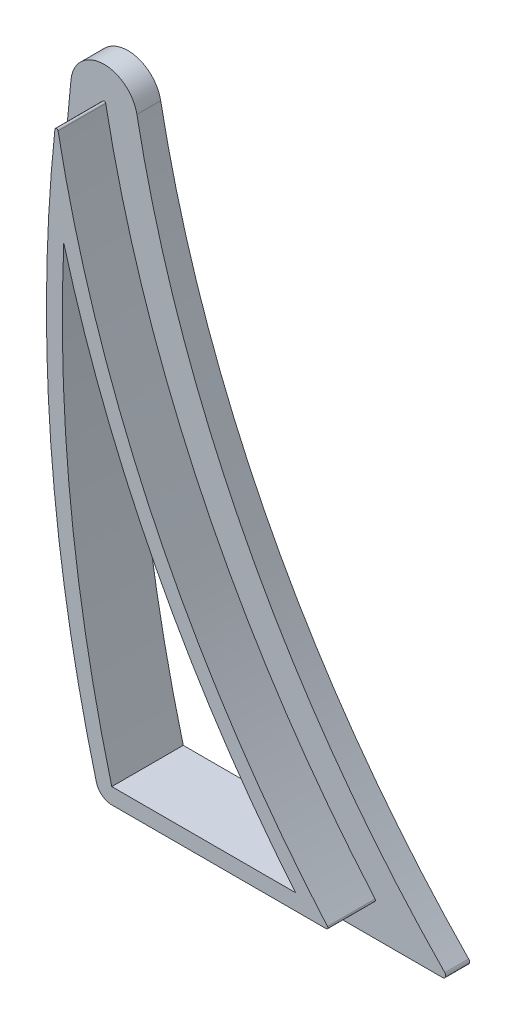
SolidWorks part; units mm, degrees
ref_plane "Plan de face" through (0, 0, 0) normal (0, 0, 1) x (1, 0, 0)
ref_plane "Plan de dessus" through (0, 0, 0) normal (0, 1, 0) x (1, 0, 0)
ref_plane "Plan de droite" through (0, 0, 0) normal (1, 0, 0) x (0, 0, -1)
sketch "Esquisse1" plane through (0, 0, 0) normal (0, 0, 1) x (1, 0, 0)
  line L2 (-4.5246, -18.1471) -> (9.1989, -18.1471)
  line L3 (-4.5246, -17.1471) -> (7.0417, -17.1471)
  arc A6 (-8.0323, 17.5812) -> (9.1989, -18.1471) centre (65.7323, 31.1376) ccw
  arc A7 (-5.4914, -17.4024) -> (-4.5246, -18.1471) centre (-4.5246, -17.1471) ccw
  arc A8 (-8.0323, 17.5812) -> (-5.4914, -17.4024) centre (86.36, 6.8529) ccw
  arc A9 (-7.5489, 10.9915) -> (7.0417, -17.1471) centre (65.7323, 31.1376) ccw
  arc A10 (-7.5489, 10.9915) -> (-4.5246, -17.1471) centre (86.36, 6.8529) ccw
extrude "Boss.-Extru.1" add sketch "Esquisse1" along normal blind 3 contours A6 A8 A7 L2 A10 A9 L3 region at (-4.8911, -17.623, 0)
fillet "Congé1" radius 0.1 1 edges at (-8.0323, 17.5812, 1.5)
sketch "Esquisse2" plane through (0, 0, 3) normal (0, 0, 1) x (1, 0, 0)
  line L0 (-4.5246, -20.1471) -> (13.7815, -20.1471)
  line L1 (-4.5246, -18.1471) -> (9.1989, -18.1471)
  line L2 (-4.5246, -18.1471) -> (9.1989, -18.1471)
  line L3 (-4.5246, -17.1471) -> (7.0417, -17.1471) construction
  line L4 (-4.5246, -17.1471) -> (7.0417, -17.1471)
  arc A0 (-10.0945, 17.1256) -> (-7.4252, -17.9131) centre (86.36, 6.8529) ccw
  arc A1 (-7.4252, -17.9131) -> (-4.5246, -20.1471) centre (-4.5246, -17.1471) ccw
  arc A2 (-5.9444, 17.3012) -> (13.7815, -20.1471) centre (65.7323, 31.1376) ccw
  arc A3 (-5.9444, 17.3012) -> (-10.0945, 17.1256) centre (-8.0064, 16.9032) ccw
  arc A4 (-7.9082, 16.9222) -> (9.1989, -18.1471) centre (65.7323, 31.1376) ccw
  arc A5 (-7.9082, 16.9222) -> (-8.1058, 16.9138) centre (-8.0064, 16.9032) ccw
  arc A6 (-8.1058, 16.9138) -> (-5.4914, -17.4024) centre (86.36, 6.8529) ccw
  arc A7 (-5.4914, -17.4024) -> (-4.5246, -18.1471) centre (-4.5246, -17.1471) ccw
  arc A8 (-7.9082, 16.9222) -> (9.1989, -18.1471) centre (65.7323, 31.1376) ccw
  arc A9 (-7.9082, 16.9222) -> (-8.1058, 16.9138) centre (-8.0064, 16.9032) ccw
  arc A10 (-8.1058, 16.9138) -> (-5.4914, -17.4024) centre (86.36, 6.8529) ccw
  arc A11 (-5.4914, -17.4024) -> (-4.5246, -18.1471) centre (-4.5246, -17.1471) ccw
  arc A12 (-7.5489, 10.9915) -> (-4.5246, -17.1471) centre (86.36, 6.8529) ccw construction
  arc A13 (-7.5489, 10.9915) -> (7.0417, -17.1471) centre (65.7323, 31.1376) ccw construction
  arc A14 (-7.5489, 10.9915) -> (-4.5246, -17.1471) centre (86.36, 6.8529) ccw
  arc A15 (-7.5489, 10.9915) -> (7.0417, -17.1471) centre (65.7323, 31.1376) ccw
  arc M11 (-4.5246, -17.1471) -> (-7.5489, 10.9915) centre (86.36, 6.8529) cw
  arc M12 (-7.5489, 10.9915) -> (7.0417, -17.1471) centre (65.7323, 31.1376) ccw
  line M13 (7.0417, -17.1471) -> (-4.5246, -17.1471)
  dimension "D1" = 0
  dimension "D2" = 2
extrude "Boss.-Extru.2" add sketch "Esquisse2" against normal blind 1.5 from offset 3 contours M11 M13 M12 | A0 A1 L0 A2 A3 region at (-2.5323, -8.1815, 3) offset against normal yes
fillet "Congé2" radius 0.2 1 edges at (13.7815, -20.1471, -0.75)
fillet "Congé3" radius 0.1 1 edges at (9.1989, -18.1471, 1.5)
